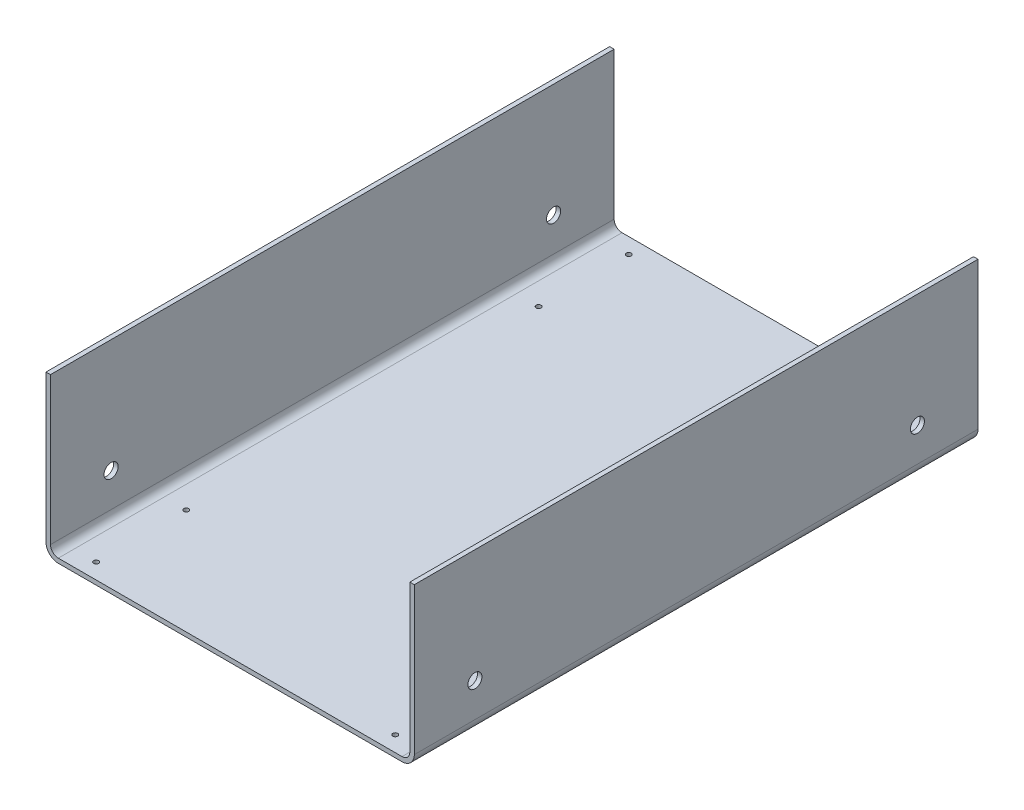
SolidWorks part; units mm, degrees
material "5052-H32"
ref_plane "Front Plane" through (0, 0, 0) normal (0, 0, 1) x (1, 0, 0)
ref_plane "Top Plane" through (0, 0, 0) normal (0, 1, 0) x (1, 0, 0)
ref_plane "Right Plane" through (0, 0, 0) normal (1, 0, 0) x (0, 0, -1)
sketch "Sketch1" plane through (0, 0, 0) normal (0, 0, 1) x (1, 0, 0)
  line L8 (127.5, 110) -> (127.5, 0)
  line L9 (-127.5, 0) -> (127.5, 0)
  line L10 (-127.5, 0) -> (-127.5, 110)
  line L11 (130.68, 110) -> (130.68, -3.18)
  line L12 (-130.68, -3.18) -> (130.68, -3.18)
  line L13 (-130.68, -3.18) -> (-130.68, 110)
  line L14 (127.5, 110) -> (130.68, 110)
  line L15 (-127.5, 110) -> (-130.68, 110)
  point P5 (0, 0)
  dimension "D2" = 110
  dimension "D4" = 110
  dimension "D3" = 255
  dimension "D1" = 3.18
extrude "Boss-Extrude1" add sketch "Sketch1" along normal blind 400
fillet "Inside Fillet" radius 5.5563 2 edges at (127.5, 0, 200) (-127.5, 0, 200)
fillet "Outside Fillet" radius 8.73 2 edges at (-130.68, -3.18, 200) (130.68, -3.18, 200)
sketch "Sketch2" plane through (130.68, 0, 0) normal (1, 0, 0) x (0, 0, -1)
  line L1 (-400, 5.55) -> (-400, 110) construction
  line L2 (0, 5.55) -> (0, 110) construction
  line L4 (-357, 29.5) -> (-357, 0) construction
  line L7 (-43, 29.5) -> (-43, 0) construction
  circle A0 centre (-357, 29.5) radius 5
  circle A1 centre (-43, 29.5) radius 5
  dimension "D4" = 10
  dimension "D2" = 29.5
  dimension "D6" = 29.5
  dimension "D1" = 43
  dimension "D5" = 43
extrude "Bearing Holes" cut sketch "Sketch2" against normal up to surface (261.36 mm away) up to face at (-130.68, 57.775, 200)
sketch "Sketch3" plane through (0, 0, 0) normal (0, 1, 0) x (1, 0, 0)
  line L0 (-106.15, -325) -> (-106.15, -389) construction
  line L1 (121.9437, -400) -> (-121.9438, -400) construction
  line L2 (-127.5, -400) -> (-127.5, 0) construction
  line L3 (-130.68, -200) -> (130.68, -200) construction
  line L4 (-130.68, -400) -> (-130.68, 0) construction
  line L5 (130.68, -400) -> (130.68, 0) construction
  line L6 (0, -400) -> (0, -200) construction
  line L7 (-106.15, -75) -> (-106.15, -11) construction
  line L8 (106.15, -75) -> (106.15, -11) construction
  line L9 (106.15, -325) -> (106.15, -389) construction
  circle A0 centre (-106.15, -325) radius 1.7526
  circle A1 centre (-106.15, -389) radius 1.7526
  circle A2 centre (-106.15, -11) radius 1.7526
  circle A3 centre (-106.15, -75) radius 1.7526
  circle A4 centre (106.15, -75) radius 1.7526
  circle A5 centre (106.15, -11) radius 1.7526
  circle A6 centre (106.15, -389) radius 1.7526
  circle A7 centre (106.15, -325) radius 1.7526
  point P4 (-106.15, -357)
  dimension "D4" = 3.5052
  dimension "D5" = 3.5052
  dimension "D1" = 64
  dimension "D2" = 43
  dimension "D3" = 21.35
extrude "Motor Mount Holes" cut sketch "Sketch3" against normal up to next
equation "\"W\"= 255"
equation "\"L\"= 400"
equation "\"Offset\"= 30"
equation "\"H\"= 110"
equation "\"Compartment Width\"= 80"
equation "\"T\"= 4.7625 * 2 / 3"
equation "\"Inside Fillet Radius\"= 5.55625"
equation "\"Hole\"=15"
equation "\"Wheel to Wall\"= 43"
equation "\"D3@Sketch1\"=\"W\""
equation "\"D2@Sketch1\"=\"H\""
equation "\"D4@Sketch1\"=\"H\""
equation "\"D1@Boss-Extrude1\"=\"L\""
equation "\"D1@Inside Fillet\"=\"Inside Fillet Radius\""
equation "\"D1@Outside Fillet\"=\"Inside Fillet Radius\"+\"T\""
equation "\"D1@Sketch2\"=\"Wheel to Wall\""
equation "\"D5@Sketch2\"=\"Wheel to Wall\""
equation "\"D2@Sketch3\"=\"Wheel to Wall\""
